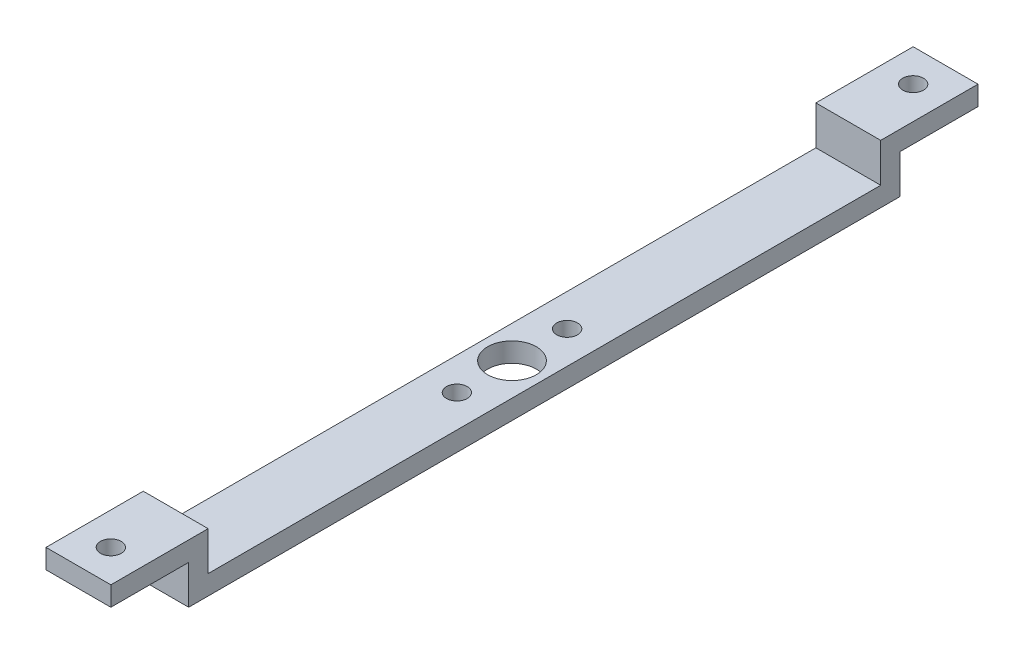
SolidWorks part; units mm, degrees
ref_plane "Alzado" through (0, 0, 0) normal (0, 0, 1) x (1, 0, 0)
ref_plane "Planta" through (0, 0, 0) normal (0, 1, 0) x (1, 0, 0)
ref_plane "Vista lateral" through (0, 0, 0) normal (1, 0, 0) x (0, 0, -1)
sketch "Croquis1" plane through (0, 0, 0) normal (1, 0, 0) x (0, 0, -1)
  line L0 (0, 0) -> (-61.85, 0) construction
  line L1 (-61.85, 0) -> (-66.85, 0)
  line L2 (-61.85, 0) -> (-51.85, 0)
  line L3 (-66.85, 0) -> (-66.85, -3)
  line L4 (-51.85, 0) -> (-51.85, -6)
  line L5 (-51.85, -6) -> (-54.85, -6) construction
  line L6 (-66.85, -3) -> (-54.85, -3)
  line L7 (-54.85, -3) -> (-54.85, -6)
  line L8 (-54.85, -6) -> (-54.85, -9)
  line L9 (-51.85, -6) -> (51.85, -6)
  line L10 (-54.85, -9) -> (54.85, -9)
  line L11 (0, 0) -> (0, -17.8995) construction
  line L12 (51.85, -6) -> (54.85, -6) construction
  line L13 (54.85, -6) -> (54.85, -9)
  line L14 (54.85, -3) -> (54.85, -6)
  line L15 (66.85, -3) -> (54.85, -3)
  line L16 (51.85, 0) -> (51.85, -6)
  line L17 (66.85, 0) -> (66.85, -3)
  line L18 (61.85, 0) -> (51.85, 0)
  line L19 (61.85, 0) -> (66.85, 0)
  point P14 (0, -6)
  point P15 (0, -9)
  dimension "D1" = 61.85
  dimension "D2" = 5
  dimension "D3" = 10
  dimension "D4" = 3
  dimension "D5" = 6
  dimension "D6" = 3
  dimension "D7" = 3
extrude "Saliente-Extruir1" add sketch "Croquis1" along normal blind 10
sketch "Croquis2" plane through (0, -6, 0) normal (0, 1, 0) x (1, 0, 0)
  line L0 (0, 0) -> (0, -61.85) construction
  line L1 (0, -51.85) -> (0, -66.85) construction
  line L2 (0, -61.85) -> (10, -61.85) construction
  line L3 (10, -51.85) -> (10, -66.85) construction
  line L4 (0, 0) -> (18.9642, 0) construction
  line L5 (5, 51.85) -> (5, -51.85) construction
  line L6 (10, 51.85) -> (0, 51.85) construction
  line L7 (10, -51.85) -> (0, -51.85) construction
  line L8 (5, 0) -> (5, -8.5) construction
  circle A0 centre (5, -61.85) radius 1.6
  circle A1 centre (5, 61.85) radius 1.6
  circle A2 centre (5, -8.5) radius 1.6
  circle A3 centre (5, 8.5) radius 1.6
  dimension "D2" = 3.2
  dimension "D4" = 3.2
  dimension "D1" = 61.85
  dimension "D3" = 8.5
extrude "Cortar-Extruir1" cut sketch "Croquis2" against normal blind 10
extrude "Cortar-Extruir2" cut sketch "Croquis2<2>" along normal blind 10
sketch "Croquis2<2>" plane through (0, -6, 0) normal (0, 1, 0) x (1, 0, 0) same geometry as "Croquis2"
sketch "Croquis3" plane through (0, -6, 0) normal (0, 1, 0) x (1, 0, 0)
  line L0 (5, 8.5) -> (5, -8.5) construction
  circle A0 centre (5, 0) radius 3.75
  dimension "D1" = 7.5
extrude "Cortar-Extruir3" cut sketch "Croquis3" against normal blind 10
